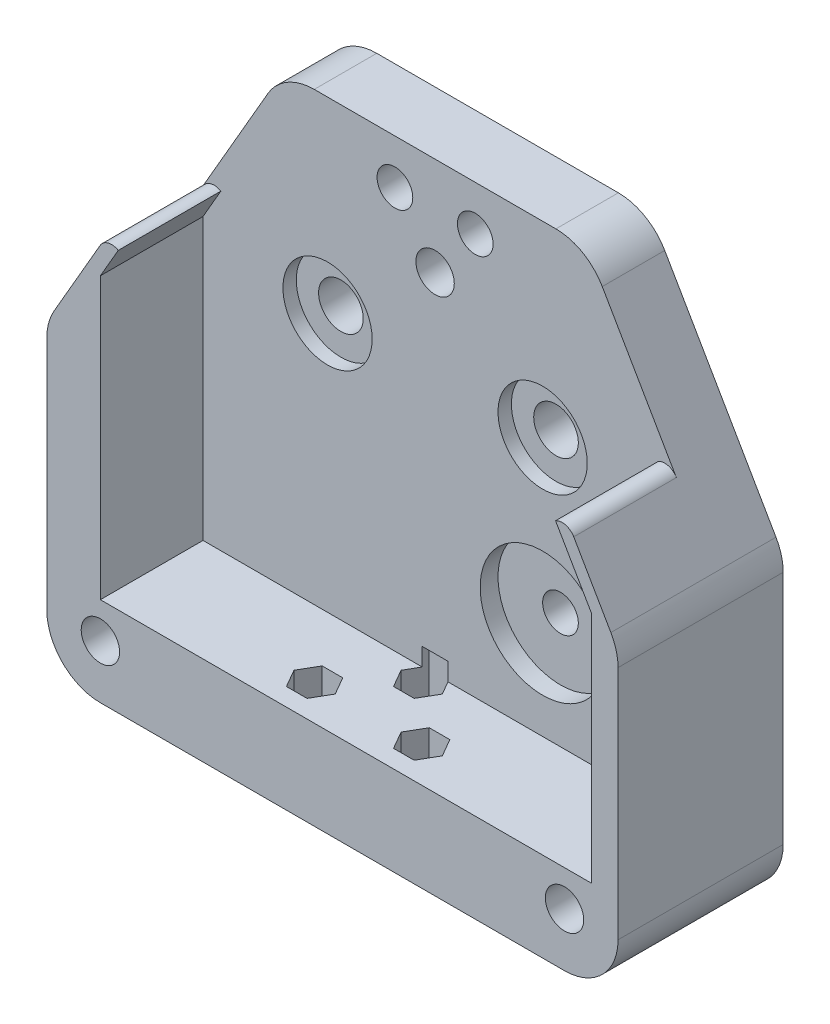
SolidWorks part; units mm, degrees
material "ABS"
ref_plane "Спереди" through (0, 0, 0) normal (0, 0, 1) x (1, 0, 0)
ref_plane "Сверху" through (0, 0, 0) normal (0, 1, 0) x (1, 0, 0)
ref_plane "Справа" through (0, 0, 0) normal (1, 0, 0) x (0, 0, -1)
sketch "Эскиз1" plane through (0, 0, 0) normal (0, 0, 1) x (1, 0, 0)
  line L0 (0, 0) -> (64, 0)
  line L1 (64, 0) -> (64, 34.0192)
  line L2 (64, 34.0192) -> (49, 60)
  line L3 (49, 60) -> (15, 60)
  line L4 (15, 60) -> (0, 34.02)
  line L5 (0, 34.02) -> (0, 0)
  dimension "D1" = 64
  dimension "D2" = 60
  dimension "D3" = 120
  dimension "D4" = 34
  dimension "D5" = 30
  dimension "D6" = 34.02
extrude "Бобышка-Вытянуть1" add sketch "Эскиз1" along normal blind 7
sketch "Эскиз3" plane through (0, 0, 7) normal (0, 0, 1) x (1, 0, 0)
  line L0 (0, 0) -> (64, 0)
  line L1 (64, 0) -> (64, 34.0192)
  line L2 (64, 34.0192) -> (58.2904, 43.9086)
  line L3 (64, 34.0192) -> (49, 60) construction
  line L4 (58.2904, 43.9086) -> (57, 43.1636)
  line L5 (57, 43.1636) -> (61, 36.2354)
  line L6 (61, 36.2354) -> (61, 10)
  line L7 (61, 10) -> (6, 10)
  line L8 (6, 10) -> (6, 41.4321)
  line L9 (6, 41.4321) -> (8, 44.8961)
  line L10 (8, 44.8961) -> (6.7097, 45.6412)
  line L11 (15, 60) -> (0, 34.02) construction
  line L12 (6.7097, 45.6412) -> (0, 34.02)
  line L13 (0, 34.02) -> (0, 0)
  dimension "D1" = 55
  dimension "D2" = 6
  dimension "D3" = 10
  dimension "D4" = 4
  dimension "D5" = 8
  dimension "D6" = 1.49
  dimension "D7" = 1.49
extrude "Бобышка-Вытянуть2" add sketch "Эскиз3" along normal blind 11.5
fillet "Скругление1" radius 6 6 edges at (64, 34.0192, 9.25) (49, 60, 3.5) (15, 60, 3.5) (0, 34.02, 9.25) (0, 0, 9.25) (64, 0, 9.25)
fillet "Скругление2" radius 1.49 2 edges at (58.2904, 43.9086, 12.75) (6.7097, 45.6412, 12.75)
hole_wizard "Зенковка для  винта с плоской головкой M44" positions "Эскиз13" profile "Эскиз14" countersink size "M4" standard "Ansi Metric" end condition through all
sketch "Эскиз13" plane through (0, 0, 0) normal (0, 0, -1) x (-1, 0, 0)
  line L3 (-32, 62.7004) -> (-32, -1.1162) construction
  line L5 (-45.5359, 60) -> (-18.4641, 60) construction
  line L6 (-6, 0) -> (-58, 0) construction
  line L7 (-64, 6) -> (-64, 32.4115) construction
  point P0 (-5.9999, 6)
  point P2 (-58, 6)
  point P4 (-32, 49)
  point P34 (-32, 60)
  dimension "D1" = 11
  dimension "D2" = 6
  dimension "D3" = 6
sketch "Эскиз14" plane through (5.9999, 6, 0) normal (1, 0, 0) x (0, 1, 0)
  line L0 (0, 0) -> (0, 18.5)
  line L1 (0, 18.5) -> (2.15, 18.5)
  line L2 (2.15, 18.5) -> (2.15, 2.2)
  line L3 (2.15, 2.2) -> (4.35, 0)
  line L5 (4.35, 0) -> (0, 0)
  line L6 (-2.15, 2.2) -> (-4.35, 0) construction
  line L11 (0, -3.8306) -> (0, 22.0892) construction
  dimension "Диаметр сквозного отверстия" = 4.3
  dimension "Глубина сквозного отверстия" = 18.5
  dimension "Диаметр передней зенковки" = 8.7
  dimension "Угол передней зенковки" = 90
hole_wizard "Отверстия под штифты Ø4.0 мм2" positions "Эскиз19" profile "Эскиз20" hole size "Ø4.0" standard "Ansi Metric" end condition through all
sketch "Эскиз19" plane through (0, 0, 0) normal (0, 0, -1) x (-1, 0, 0)
  line L0 (-45.5359, 60) -> (-18.4641, 60) construction
  line L1 (-64, 6) -> (-64, 32.4115) construction
  line L8 (-32, 62.4273) -> (-32, -3.8376) construction
  point P0 (-36.5, 55)
  point P2 (-27.4999, 55)
  point P94 (-32, 60)
  dimension "D1" = 5
  dimension "D2" = 27.5
sketch "Эскиз20" plane through (36.5, 55, 0) normal (1, 0, 0) x (0, 1, 0)
  line L0 (0, 0) -> (0, 18.5)
  line L1 (0, 18.5) -> (2, 18.5)
  line L2 (2, 18.5) -> (2, 0)
  line L5 (2, 0) -> (0, 0)
  line L11 (0, -3.866) -> (0, 11.4564) construction
  dimension "Диаметр сквозного отверстия" = 4
  dimension "Глубина сквозного отверстия" = 18.5
hole_wizard "Отверстия под штифты Ø5.0 мм1" positions "Эскиз21" profile "Эскиз22" hole size "Ø5.0" standard "Ansi Metric" end condition through all
sketch "Эскиз21" plane through (0, 0, 0) normal (0, 0, -1) x (-1, 0, 0)
  line L0 (-45.5359, 60) -> (-18.4641, 60) construction
  line L1 (-64, 6) -> (-64, 32.4115) construction
  line L2 (-32, 62.1722) -> (-32, -3.1086) construction
  point P0 (-44.05, 39)
  point P2 (-19.9499, 39)
  point P18 (-32, 60)
  dimension "D1" = 21
  dimension "D2" = 19.95
sketch "Эскиз22" plane through (44.05, 39, 0) normal (1, 0, 0) x (0, 1, 0)
  line L0 (0, 0) -> (0, 18.5)
  line L1 (0, 18.5) -> (2.5, 18.5)
  line L2 (2.5, 18.5) -> (2.5, 0)
  line L5 (2.5, 0) -> (0, 0)
  line L11 (0, -6.35) -> (0, 13.5001) construction
  dimension "Диаметр сквозного отверстия" = 5
  dimension "Глубина сквозного отверстия" = 18.5
ref_plane "Плоскость2" through (0, 10, 0) normal (0, -1, 0) x (-1, 0, 0)
hole_wizard "Отверстия под штифты Ø4.0 мм3" positions "Эскиз52" profile "Эскиз53" hole size "Ø4.0" standard "Ansi Metric" end condition through all
sketch "Эскиз52" plane through (0, 0, 7) normal (0, 0, 1) x (1, 0, 0)
  line L0 (64, 6) -> (64, 32.4115) construction
  line L1 (6, 0) -> (58, 0) construction
  point P0 (44.05, 21)
  dimension "D1" = 19.95
  dimension "D2" = 21
sketch "Эскиз53" plane through (44.05, 21, 7) normal (1, 0, 0) x (0, -1, 0)
  line L0 (0, 0) -> (0, 7)
  line L1 (0, 7) -> (2, 7)
  line L2 (2, 7) -> (2, 0)
  line L5 (2, 0) -> (0, 0)
  line L11 (0, -6.35) -> (0, 24.92) construction
  dimension "Диаметр сквозного отверстия" = 4
  dimension "Глубина сквозного отверстия" = 7
sketch "Эскиз54" plane through (0, 0, 7) normal (0, 0, 1) x (1, 0, 0)
  line L0 (64, 6) -> (64, 32.4115) construction
  line L1 (6, 0) -> (58, 0) construction
  circle A0 centre (44.05, 21) radius 7
  dimension "D1" = 14
  dimension "D2" = 19.95
  dimension "D3" = 21
extrude "Вырез-Вытянуть5" cut sketch "Эскиз54" against normal blind 2
sketch "Эскиз55" plane through (0, 0, 7) normal (0, 0, 1) x (1, 0, 0)
  circle A0 centre (19.9499, 39) radius 5
  circle A1 centre (19.9499, 39) radius 2.5 construction
  circle A2 centre (44.05, 39) radius 5
  circle A3 centre (44.05, 39) radius 2.5 construction
  dimension "D1" = 10
  dimension "D2" = 10
extrude "Вырез-Вытянуть9" cut sketch "Эскиз55" against normal blind 1.5
hole_wizard "Сверло под метчик  спиральное M2.21" positions "Эскиз56" profile "Эскиз57" hole size "M2.2x0.45" standard "Ansi Metric"
sketch "Эскиз56" plane through (0, 0, 0) normal (0, -1, 0) x (-1, 0, 0)
  line L0 (-6, -18.5) -> (-58, -18.5) construction
  line L1 (-32, -19.1422) -> (-32, -5.5593) construction
  line L3 (-6, -18.5) -> (-6, 0) construction
  point P0 (-26, -14.5)
  point P2 (-38, -14.5)
  point P15 (-32, -18.5)
  dimension "D1" = 4
  dimension "D2" = 20
sketch "Эскиз57" plane through (26, 0, 14.5) normal (1, 0, 0) x (0, 0, -1)
  line L0 (0, 0) -> (0, 10.6009)
  line L1 (0, 10.6009) -> (1, 10)
  line L2 (1, 10) -> (1, 0)
  line L5 (1, 0) -> (0, 0)
  line L10 (0, 10.6009) -> (-1, 10) construction
  line L11 (0, -6.35) -> (0, 14.5802) construction
  dimension "Диаметр отверстия" = 2
  dimension "Глубина отверстия" = 10
  dimension "Угол заточки сверла" = 118
sketch "Эскиз58" plane through (0, 10, 0) normal (0, 1, 0) x (1, 0, 0)
  line L0 (26, -10.8602) -> (26, -17.0191) construction
  line L1 (28.3094, -14.5) -> (27.1547, -12.5)
  line L2 (27.1547, -12.5) -> (24.8453, -12.5)
  line L3 (24.8453, -12.5) -> (23.6906, -14.5)
  line L4 (23.6906, -14.5) -> (24.8453, -16.5)
  line L5 (24.8453, -16.5) -> (27.1547, -16.5)
  line L6 (27.1547, -16.5) -> (28.3094, -14.5)
  line L9 (38, -10.8602) -> (38, -17.0191) construction
  line L10 (40.3094, -14.5) -> (39.1547, -12.5)
  line L11 (39.1547, -12.5) -> (36.8453, -12.5)
  line L12 (36.8453, -12.5) -> (35.6906, -14.5)
  line L13 (35.6906, -14.5) -> (36.8453, -16.5)
  line L14 (36.8453, -16.5) -> (39.1547, -16.5)
  line L15 (39.1547, -16.5) -> (40.3094, -14.5)
  circle A0 centre (26, -14.5) radius 2 construction
  circle A1 centre (38, -14.5) radius 2 construction
  dimension "D1" = 4
  dimension "D2" = 30
  dimension "D3" = 4
  dimension "D4" = 30
extrude "Вырез-Вытянуть11" cut sketch "Эскиз58" against normal blind 4
hole_wizard "Сверло под метчик  спиральное M2.22" positions "Эскиз59" profile "Эскиз60" hole size "M2.2x0.45" standard "Ansi Metric"
sketch "Эскиз59" plane through (0, 0, 0) normal (0, -1, 0) x (-1, 0, 0)
  line L0 (-6, -18.5) -> (-58, -18.5) construction
  line L1 (-58, 0) -> (-58, -18.5) construction
  point P0 (-32, -8.5)
  dimension "D1" = 10
  dimension "D2" = 26
sketch "Эскиз60" plane through (32, 0, 8.5) normal (1, 0, 0) x (0, 0, -1)
  line L0 (0, 0) -> (0, 10.6009)
  line L1 (0, 10.6009) -> (1, 10)
  line L2 (1, 10) -> (1, 0)
  line L5 (1, 0) -> (0, 0)
  line L10 (0, 10.6009) -> (-1, 10) construction
  line L11 (0, -6.35) -> (0, 21.1048) construction
  dimension "Диаметр отверстия" = 2
  dimension "Глубина отверстия" = 10
  dimension "Угол заточки сверла" = 118
sketch "Эскиз61" plane through (0, 10, 0) normal (0, 1, 0) x (1, 0, 0)
  line L0 (32, -5.2203) -> (32, -10.1362) construction
  line L1 (34.3094, -8.5) -> (33.1547, -6.5)
  line L2 (33.1547, -6.5) -> (30.8453, -6.5)
  line L3 (30.8453, -6.5) -> (29.6906, -8.5)
  line L4 (29.6906, -8.5) -> (30.8453, -10.5)
  line L5 (30.8453, -10.5) -> (33.1547, -10.5)
  line L6 (33.1547, -10.5) -> (34.3094, -8.5)
  circle A0 centre (32, -8.5) radius 2 construction
  dimension "D1" = 4
  dimension "D2" = 30
extrude "Вырез-Вытянуть12" cut sketch "Эскиз61" against normal blind 4
sketch "Эскиз62" plane through (0, 10, 0) normal (0, -1, 0) x (-1, 0, 0)
  line L1 (-29.6906, -8.5) -> (-30.8453, -6.5)
  line L2 (-30.8453, -6.5) -> (-33.1547, -6.5)
  line L3 (-33.1547, -6.5) -> (-34.3094, -8.5)
  line L4 (-34.3094, -8.5) -> (-33.1547, -10.5)
  line L5 (-33.1547, -10.5) -> (-30.8453, -10.5)
  line L6 (-30.8453, -10.5) -> (-29.6906, -8.5)
  line L8 (-32, -5.0947) -> (-32, -10.6745) construction
  circle A0 centre (-32, -8.5) radius 2 construction
  circle A1 centre (-32, -8.5) radius 1 construction
  dimension "D1" = 4
  dimension "D2" = 30
extrude "Вырез-Вытянуть13" cut sketch "Эскиз62" against normal blind 2
